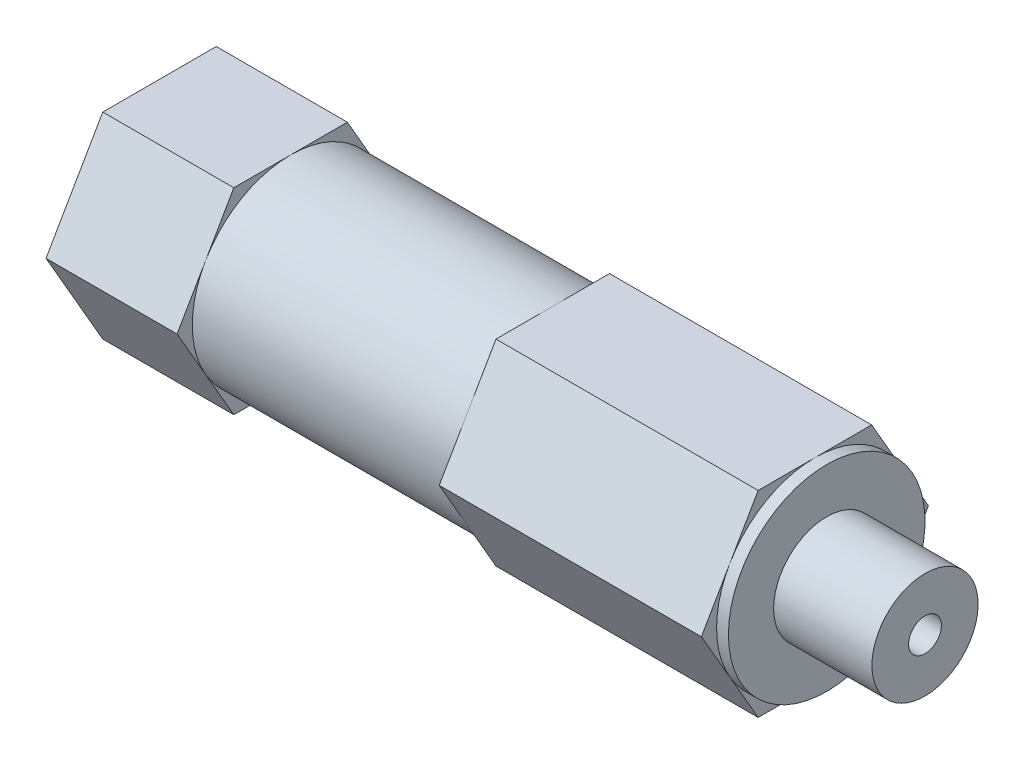
SolidWorks part; units mm, degrees
material "AISI 316 Stainless Steel Sheet (SS)"
ref_plane "Front Plane" through (0, 0, 0) normal (0, 0, 1) x (1, 0, 0)
ref_plane "Top Plane" through (0, 0, 0) normal (0, 1, 0) x (1, 0, 0)
ref_plane "Right Plane" through (0, 0, 0) normal (1, 0, 0) x (0, 0, -1)
sketch "Sketch1" plane through (0, 0, 0) normal (0, 0, 1) x (1, 0, 0)
  line L0 (0, 0) -> (36.4858, 0) construction
  line L1 (0, 9.525) -> (64.643, 9.525)
  line L6 (0, 0) -> (0, 9.525) construction
  line L7 (0, 9.525) -> (0, 4.7625)
  line L8 (0, 4.7625) -> (23.7944, 4.7625)
  line L9 (23.7944, 4.7625) -> (25.3082, 2.413)
  line L10 (25.3082, 2.413) -> (31.9175, 2.413)
  line L11 (31.9175, 2.413) -> (36.7954, 5.5559)
  line L12 (36.7954, 5.5559) -> (36.7954, 7.5369)
  line L13 (36.7954, 7.5369) -> (40.4579, 7.5369)
  line L14 (40.4579, 7.5369) -> (40.4579, 4.5892)
  line L15 (40.4579, 4.5892) -> (59.7788, 4.5892)
  line L16 (59.7788, 4.5892) -> (59.7788, 1.5875)
  line L17 (59.7788, 1.5875) -> (74.168, 1.5875)
  line L18 (74.168, 1.5875) -> (74.168, 5.1435)
  line L19 (74.168, 5.1435) -> (64.643, 5.1435)
  line L20 (64.643, 5.1435) -> (64.643, 9.525)
  point P4 (65.4308, 14.8868)
  point P6 (34.0451, 7.7695)
  point P7 (59.823, 7.3485)
  point P8 (19.5575, 10.2903)
  point P22 (0, 0)
  point P24 (36.6565, 7.3485)
  point P25 (22.5912, 8.4517)
  point P26 (30.0375, 3.8552)
  point P27 (34.9374, 5.179)
  point P28 (0, 0)
  point P29 (35.3787, 7.3853)
  point P30 (64.392, 6.1718)
  dimension "D1" = 74.168
  dimension "D2" = 19.05
  dimension "D3" = 10.287
  dimension "D4" = 9.525
  dimension "D5" = 4.826
  dimension "D6" = 3.175
  dimension "D7" = 9.525
revolve "Revolve1" add sketch "Sketch1" angle 360 about L0
sketch "Sketch8" plane through (0, 0, 0) normal (-1, 0, 0) x (0, 0, 1)
  line L0 (0, 0) -> (10.9985, 0) construction
  line L1 (-10.9985, 0) -> (-5.4993, -9.525)
  line L2 (-5.4993, -9.525) -> (5.4993, -9.525)
  line L3 (5.4993, -9.525) -> (10.9985, 0)
  line L4 (10.9985, 0) -> (5.4993, 9.525)
  line L5 (5.4993, 9.525) -> (-5.4993, 9.525)
  line L6 (-5.4993, 9.525) -> (-10.9985, 0)
  circle A0 centre (0, 0) radius 9.525 construction
  circle A1 centre (0, 0) radius 9.525
  circle A2 centre (0, 0) radius 9.525 construction
  circle M10 centre (0, 0) radius 9.525
extrude "Boss-Extrude1" add sketch "Sketch8" against normal blind 12.7 contours L4 L5 M10 | L5 L6 M10 | L6 L1 M10 | L1 L2 M10 | L2 L3 M10 | L3 L4 M10 region at (0, 0, -9.8447) region at (0, -8.5257, -4.9223) region at (0, 8.5257, -4.9223) region at (0, -8.5257, 4.9223) region at (0, 8.5257, 4.9223) region at (0, 0, 9.8447)
extrude "Boss-Extrude2" add sketch "Sketch8<3>" against normal blind 25.4 from offset 38.1 contours L4 L5 M10 | L5 L6 M10 | L6 L1 M10 | L1 L2 M10 | L2 L3 M10 | L3 L4 M10 region at (0, 0, -9.8447) region at (0, -8.5257, -4.9223) region at (0, 8.5257, -4.9223) region at (0, -8.5257, 4.9223) region at (0, 8.5257, 4.9223) region at (0, 0, 9.8447) offset against normal yes
sketch "Sketch8<3>" plane through (0, 0, 0) normal (-1, 0, 0) x (0, 0, 1) same geometry as "Sketch8"
